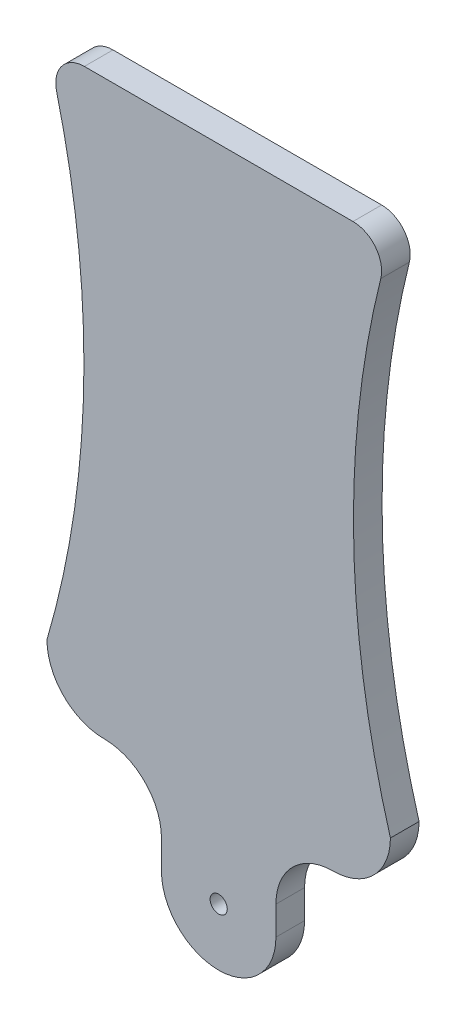
SolidWorks part; units mm, degrees
material "Acrílico (médio-alto impacto)"
ref_plane "Plano frontal" through (0, 0, 0) normal (0, 0, 1) x (1, 0, 0)
ref_plane "Plano superior" through (0, 0, 0) normal (0, 1, 0) x (1, 0, 0)
ref_plane "Plano direito" through (0, 0, 0) normal (1, 0, 0) x (0, 0, -1)
sketch "Esboço1" plane through (0, 0, 0) normal (0, 0, 1) x (1, 0, 0)
  line L0 (-14.0897, 13.1354) -> (-14.0897, 28.1354)
  line L1 (5.9103, 13.1354) -> (5.9103, 28.1354)
  line L2 (5.9103, 28.1354) -> (25.9103, 28.1354)
  line L3 (-34.0897, 128.1354) -> (25.9103, 128.1354)
  line L4 (-34.0897, 128.1354) -> (-34.0897, 28.1354)
  line L5 (-34.0897, 28.1354) -> (-14.0897, 28.1354)
  line L6 (25.9103, 128.1354) -> (25.9103, 28.1354)
  arc A0 (-14.0897, 13.1354) -> (5.9103, 13.1354) centre (-4.0897, 13.1354) ccw
  dimension "D1" = 20
  dimension "D2" = 100
  dimension "D3" = 20
  dimension "D4" = 20
extrude "Ressalto-extrusão1" add sketch "Esboço1" along normal blind 5
sketch "Esboço2" plane through (0, 0, 5) normal (0, 0, 1) x (1, 0, 0)
  circle A0 centre (-4.0897, 13.1354) radius 1.5
  dimension "D1" = 3
extrude "Corte-extrusão1" cut sketch "Esboço2" against normal blind 5
fillet "Filete1" radius 10 4 edges at (5.9103, 28.1354, 2.5) (25.9103, 28.1354, 2.5) (-34.0897, 28.1354, 2.5) (-14.0897, 28.1354, 2.5)
sketch "Esboço3" plane through (0, 0, 5) normal (0, 0, 1) x (1, 0, 0)
  line L0 (-4.0897, 158.1354) -> (-4.0897, 126.1599) construction
  line L2 (-34.0897, 128.1354) -> (-34.0897, 38.1354)
  line L3 (-34.0897, 38.1354) -> (-33.4511, 37.9723)
  line L4 (25.9103, 128.1354) -> (25.9103, 38.1354)
  arc A0 (-34.0897, 38.1354) -> (-34.0897, 128.1354) centre (-187.6312, 83.1354) ccw
  arc A1 (25.9103, 38.1354) -> (25.9103, 128.1354) centre (179.4519, 83.1354) cw
  line M6 (25.9103, 38.1354) -> (25.9103, 128.1354)
  line M8 (-34.0897, 128.1354) -> (-34.0897, 38.1354)
  dimension "D1" = 160
extrude "Corte-extrusão2" cut sketch "Esboço3" against normal blind 5 contours A0 M8 | A1 M6 region at (-31.5018, 83.1354, 5) region at (23.3224, 83.1354, 5)
fillet "Filete2" radius 5 2 edges at (25.9103, 128.1354, 2.5) (-34.0897, 128.1354, 2.5)
